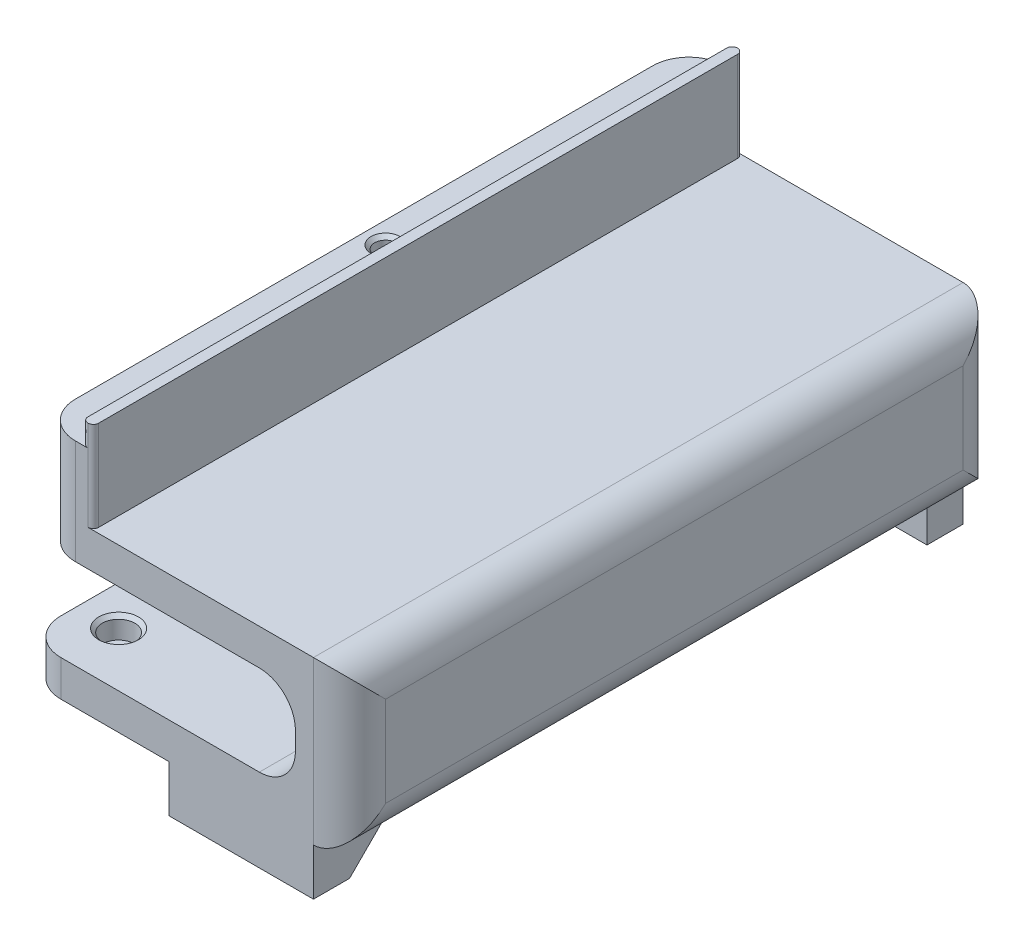
SolidWorks part; units mm, degrees
ref_plane "Front Plane" through (0, 0, 0) normal (0, 0, 1) x (1, 0, 0)
ref_plane "Top Plane" through (0, 0, 0) normal (0, 1, 0) x (1, 0, 0)
ref_plane "Right Plane" through (0, 0, 0) normal (1, 0, 0) x (0, 0, -1)
sketch "Sketch1" plane through (0, 0, 0) normal (0, 0, 1) x (1, 0, 0)
  line L1 (0, 0) -> (90, 0)
  line L2 (0, 0) -> (0, 10)
  line L3 (0, 10) -> (90, 10)
  line L4 (90, 0) -> (90, 10)
  line L5 (90, 10) -> (75, 10)
  line L6 (90, 10) -> (90, 35)
  line L7 (90, 35) -> (75, 35)
  line L8 (75, 10) -> (75, 35)
  line L9 (90, 35) -> (4, 35)
  line L10 (90, 35) -> (90, 45)
  line L11 (90, 45) -> (4, 45)
  line L12 (4, 35) -> (4, 45)
  line L13 (4, 45) -> (19, 45)
  line L14 (4, 45) -> (4, 64)
  line L15 (4, 64) -> (19, 64)
  line L16 (19, 45) -> (19, 64)
  line L17 (19, 64) -> (16, 64)
  line L18 (19, 64) -> (19, 70)
  line L19 (19, 70) -> (16, 70)
  line L20 (16, 64) -> (16, 70)
  dimension "D1" = 10
  dimension "D2" = 90
  dimension "D3" = 25
  dimension "D4" = 15
  dimension "D5" = 10
  dimension "D6" = 86
  dimension "D7" = 19
  dimension "D8" = 15
  dimension "D9" = 6
  dimension "D10" = 3
extrude "Boss-Extrude1" add sketch "Sketch1" along normal blind 180 contours L1 L4 L3 L2 | L8 L3 L6 L7 | L12 L9 L7 L10 L11 | L20 L15 L18 L19 | L14 L15 L16 L13 region at (45, 5, 0) region at (82.5, 22.5, 0) region at (47, 40, 0) region at (17.5, 67, 0)
sketch "Sketch2" plane through (0, 10, 0) normal (0, 1, 0) x (1, 0, 0)
  line L0 (11, -165) -> (11, 38.7826) construction
  line L1 (11, -90) -> (113.1401, -90) construction
  line L2 (0, -180) -> (0, 0) construction
  line L3 (90, -180) -> (19, -180) construction
  circle A1 centre (11, -65) radius 2.6
  circle A2 centre (11, -15) radius 2.6
  circle A3 centre (11, -65) radius 2.6
  circle A4 centre (11, -115) radius 2.6
  circle A5 centre (11, -115) radius 2.6
  circle A6 centre (11, -165) radius 2.6
  circle A7 centre (11, -65) radius 4.5
  circle A8 centre (11, -15) radius 4.5
  circle A9 centre (11, -65) radius 4.5
  circle A10 centre (11, -115) radius 4.5
  circle A11 centre (11, -115) radius 4.5
  circle A12 centre (11, -165) radius 4.5
  dimension "D1" = 5.2
  dimension "D6" = 11
  dimension "D2" = 25
  dimension "D7" = 90
  dimension "D5" = 1.9
  dimension "D3" = 2
  dimension "D4" = 3
extrude "Cut-Extrude1" cut sketch "Sketch2" against normal through all contours A2 | A1 | A4 | A6
extrude "Cut-Extrude2" cut sketch "Sketch2<3>" against normal blind 6 contours A8 | A7 | A10 | A12
sketch "Sketch2<3>" plane through (0, 10, 0) normal (0, 1, 0) x (1, 0, 0) same geometry as "Sketch2"
sketch "Sketch3" plane through (0, 64, 0) normal (0, 1, 0) x (1, 0, 0)
  line L0 (4, -90) -> (16, -90) construction
  line L1 (4, -180) -> (4, 0) construction
  line L2 (16, -180) -> (16, 0) construction
  circle A0 centre (10, -90) radius 3.05
  dimension "D1" = 6.1
extrude "Cut-Extrude3" cut sketch "Sketch3" against normal blind 8
fillet "Fillet4" radius 10 10 edges at (4, 49.5, 0) (4, 49.5, 180) (90, 22.5, 180) (90, 22.5, 0) (0, 5, 0) (0, 5, 180) (75, 10, 90) (75, 35, 90) (90, 45, 90) (90, 0, 90)
chamfer "Chamfer1" distance 1 angle 45 5 edges at (11, 10, 169.5) (11, 10, 119.5) (10, 64, 93.05) (11, 10, 69.5) (11, 10, 19.5)
fillet "Fillet5" radius 1.5 4 edges at (19, 57.5, 0) (16, 67, 0) (19, 57.5, 180) (16, 67, 180)
sketch "Sketch4" plane through (0, 0, 0) normal (0, -1, 0) x (1, 0, 0)
  line L1 (80, 0) -> (40, 0)
  line L2 (80, 0) -> (80, 10)
  line L3 (80, 10) -> (40, 10)
  line L4 (40, 0) -> (40, 10)
  line L5 (80, 180) -> (40, 180)
  line L6 (80, 180) -> (80, 170)
  line L7 (80, 170) -> (40, 170)
  line L8 (40, 180) -> (40, 170)
  dimension "D1" = 40
  dimension "D2" = 40
  dimension "D3" = 10
  dimension "D4" = 10
extrude "Boss-Extrude2" add sketch "Sketch4" along normal blind 13
chamfer "Chamfer2" distance 13 angle 45 1 edges at (60, 0, 170)
